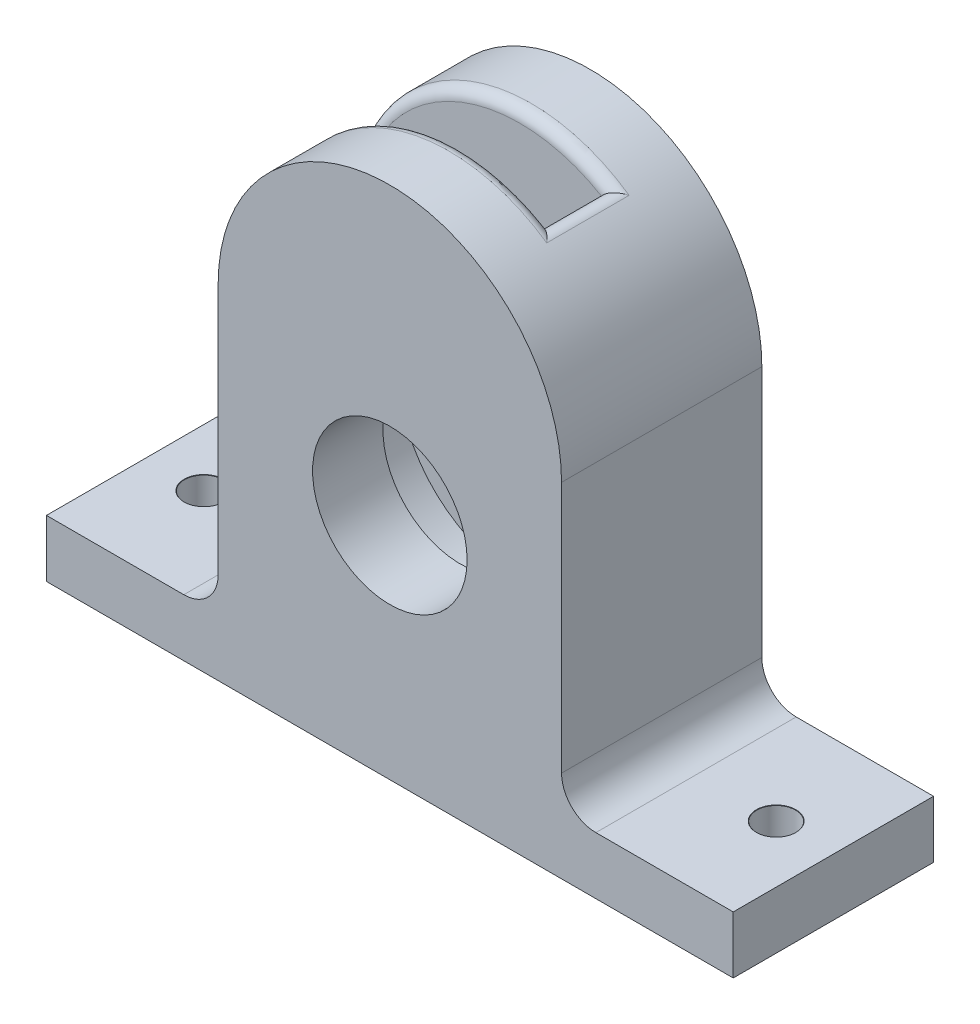
SolidWorks part; units mm, degrees
material "PLA 20%"
ref_plane "Front Plane" through (0, 0, 0) normal (0, 0, 1) x (1, 0, 0)
ref_plane "Top Plane" through (0, 0, 0) normal (0, 1, 0) x (1, 0, 0)
ref_plane "Right Plane" through (0, 0, 0) normal (1, 0, 0) x (0, 0, -1)
sketch "Sketch1" plane through (0, 0, 0) normal (0, 0, 1) x (1, 0, 0)
  line L0 (15, -15) -> (15, -20) construction
  line L2 (-15, -15) -> (-15, 10)
  line L3 (-15, 10) -> (15, 10) construction
  line L4 (15, -15) -> (15, 10)
  line L5 (0, 10) -> (0, 0) construction
  line L6 (10.439, 1.8407) -> (6.6275, 23.4564)
  line L7 (-13.6308, 16.2611) -> (-10.439, -1.8407)
  line L10 (15, -15) -> (30, -15)
  line L11 (30, -20) -> (30, -15)
  line L12 (15, -20) -> (-15, -20)
  line L13 (30, -20) -> (15, -20)
  line L14 (-30, -20) -> (-15, -20)
  line L15 (-30, -20) -> (-30, -15)
  line L16 (-15, -15) -> (-30, -15)
  line L17 (-15, -20) -> (-15, -15) construction
  circle A0 centre (0, 0) radius 6.75
  arc A1 (-15, 10) -> (15, 10) centre (0, 10) cw
  circle A2 centre (0, 0) radius 10.6
  dimension "D2" = 13.5
  dimension "D5" = 21.2
  dimension "D1" = 20
  dimension "D3" = 30
  dimension "D4" = 10
  dimension "D6" = 10
  dimension "D7" = 5
  dimension "D9" = 15
extrude "Boss-Extrude1" add sketch "Sketch1" along normal mid plane 17.5 contours A2 L7 L2 L4 A1 L6 | A2 L6 A1 L7 | A2 A0 region at (-14.2592, -2.5, 0) region at (-2.3816, 15.5523, 0) region at (-1.7886, 10.1437, 0)
extrude "Cut-Extrude1" cut sketch "Sketch1<11>" against normal mid plane 5.2 contours A2 A0 | A2 L6 A1 L7 region at (-2.3816, 15.5523, 0) region at (-1.7886, 10.1437, 0)
sketch "Sketch1<11>" plane through (0, 0, 0) normal (0, 0, 1) x (1, 0, 0) same geometry as "Sketch1"
fillet "Fillet3" radius 1 4 edges at (-13.6308, 16.2611, 0) (-5.0204, 24.1349, -2.6) (6.6275, 23.4564, 0) (-5.0204, 24.1349, 2.6) type face fillet first side face at (0, 17.5, 0) second side face at (-12.0349, 7.2102, 0) second side face at (6.75, 0, 2.6) second side face at (8.5332, 12.6486, 0) second side face at (6.75, 0, -2.6)
fillet "Fillet5" radius 3 2 edges at (15, -15, 0) (-15, -15, 0)
hole_wizard "M3 Clearance Hole1" positions "Sketch6" profile "Sketch8" hole size "M3" standard "ANSI Metric" end condition through all
sketch "Sketch6" plane through (0, -15, 0) normal (0, 1, 0) x (1, 0, 0)
  line L0 (0, 0) -> (0, 6.9977) construction
  point P0 (-25, 0)
  point P10 (0, 0)
  point P11 (0, 0)
  point P12 (0, 0)
  point P13 (25, 0)
  dimension "D1" = 25
sketch "Sketch8" plane through (-25, -15, 0) normal (1, 0, 0) x (0, 0, 1)
  line L0 (0, 0) -> (0, 5)
  line L1 (0, 5) -> (1.7, 5)
  line L2 (1.7, 5) -> (1.7, 0.025)
  line L3 (1.7, 0.025) -> (1.725, 0)
  line L5 (1.725, 0) -> (0, 0)
  line L6 (-1.7, 0.025) -> (-1.725, 0) construction
  line L11 (0, -6.35) -> (0, 107.95) construction
  dimension "Thru Hole Dia." = 3.4
  dimension "Thru Hole Depth" = 5
  dimension "Near C'Sink Dia." = 3.45
  dimension "Near C'Sink Angle" = 90
